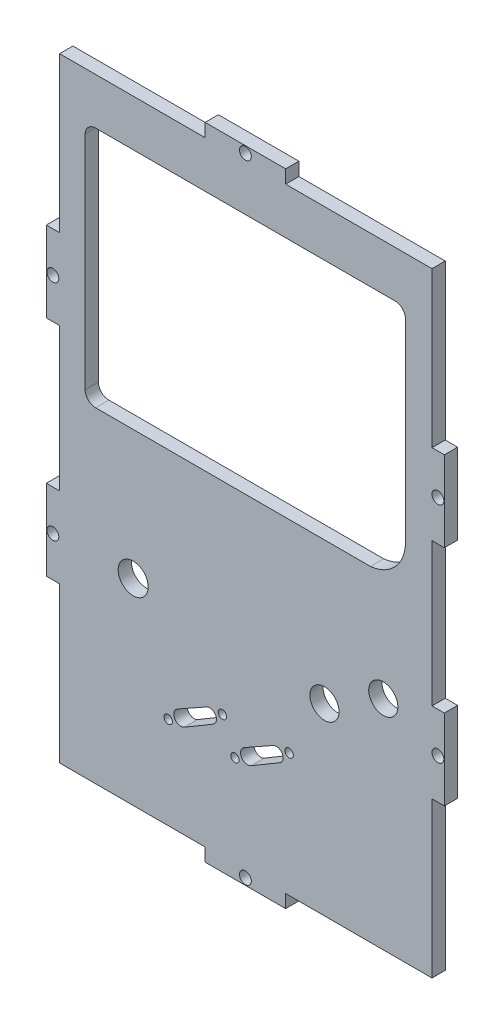
SolidWorks part; units mm, degrees
ref_plane "Front Plane" through (0, 0, 0) normal (0, 0, 1) x (1, 0, 0)
ref_plane "Top Plane" through (0, 0, 0) normal (0, 1, 0) x (1, 0, 0)
ref_plane "Right Plane" through (0, 0, 0) normal (1, 0, 0) x (0, 0, -1)
sketch "Sketch1" plane through (0, 0, 0) normal (0, 0, 1) x (1, 0, 0)
  line L0 (0.1058, 73.6301) -> (-0.0148, 62.4901) construction
  line L1 (-0.0148, 62.4901) -> (-0.0148, 56.2001) construction
  line L2 (-0.0148, 56.2001) -> (-0.0148, 10.268) construction
  line L3 (-15.4692, -49.8142) -> (-8.5409, -45.8142) construction
  line L4 (-15.4692, -49.8142) -> (0.5308, -49.8142)
  line L5 (0.5308, -49.8142) -> (7.4591, -45.8142) construction
  line L6 (-0.0148, 10.268) -> (0.1058, -73.6642) construction
  line L7 (-18.5002, -51.5642) -> (-5.5099, -44.0642) construction
  line L8 (0.5308, -49.8142) -> (7.4591, -45.8142)
  line L9 (-2.5002, -51.5642) -> (10.4901, -44.0642) construction
  line L15 (-16.3293, -29.1587) -> (-16.3293, -23.8757)
  line L20 (-0.2968, -48.3429) -> (6.6759, -44.4208)
  line L21 (8.2583, -47.1985) -> (1.3584, -51.2855)
  line L22 (-44.5392, 73.6301) -> (44.7508, 73.6301)
  line L23 (44.7508, 73.6301) -> (44.7508, -73.6642)
  line L24 (44.7508, -73.6642) -> (-44.5392, -73.6642)
  line L25 (-44.5392, -73.6642) -> (-44.5392, 73.6301)
  line L26 (-25.0598, 56.2001) -> (-25.0598, 10.268)
  line L27 (-25.0598, 10.268) -> (25.0303, 10.268)
  line L28 (25.0303, 10.268) -> (25.0303, 56.2001)
  line L29 (25.0303, 56.2001) -> (-25.0598, 56.2001)
  line L34 (35.8896, 62.4901) -> (-35.9192, 62.4901)
  line L35 (-38.4192, 59.9901) -> (-38.4192, 6.918)
  line L36 (-35.9192, 4.418) -> (29.9974, 4.418)
  line L37 (38.3896, 13.668) -> (38.3896, 59.9901)
  line L38 (-16.2968, -48.3429) -> (-9.3241, -44.4208)
  line L39 (-7.7417, -47.1985) -> (-14.6416, -51.2855)
  line L150 (42.2525, -55.0539) -> (42.2511, -54.9499)
  circle A1 centre (-5.5099, -44.0642) radius 1
  circle A2 centre (-26.9008, -26.5172) radius 3.6
  arc A3 (8.2583, -47.1985) -> (6.6759, -44.4208) centre (7.4591, -45.8142) ccw
  circle A4 centre (-18.5002, -51.5642) radius 1
  circle A5 centre (10.4901, -44.0642) radius 1
  arc A6 (-16.2968, -48.3429) -> (-14.6416, -51.2855) centre (-15.4692, -49.8142) ccw
  arc A7 (-7.7417, -47.1985) -> (-9.3241, -44.4208) centre (-8.5409, -45.8142) ccw
  circle A12 centre (-2.5002, -51.5642) radius 1
  circle A15 centre (18.9576, -29.5613) radius 3.5
  circle A16 centre (33.0683, -21.4917) radius 3.5
  arc A17 (-0.2968, -48.3429) -> (1.3584, -51.2855) centre (0.5308, -49.8142) ccw
  circle A19 centre (-32.8459, 40.326) radius 4.5
  arc A24 (38.3896, 59.9901) -> (35.8896, 62.4901) centre (35.8896, 59.9901) ccw
  arc A25 (-35.9192, 62.4901) -> (-38.4192, 59.9901) centre (-35.9192, 59.9901) ccw
  arc A26 (-38.4192, 6.918) -> (-35.9192, 4.418) centre (-35.9192, 6.918) ccw
  arc A27 (29.9974, 4.418) -> (38.3896, 13.668) centre (29.1397, 13.6282) ccw
  point P31 (-12.005, -47.8142)
  point P51 (3.995, -47.8142)
  dimension "D4" = 11.14
  dimension "D8" = 7
  dimension "D11" = 9
  dimension "D12" = 7.2
  dimension "D14" = 9.25
  dimension "D15" = 2.5
  dimension "D25" = 2
  dimension "D2" = 89.29
  dimension "D3" = 147.2943
  dimension "D5" = 25.9097
  dimension "D6" = 8.0696
  dimension "D7" = 14.1107
  dimension "D9" = 7.7861
  dimension "D10" = 22.1641
  dimension "D13" = 10.5715
  dimension "D16" = 6.29
  dimension "D17" = 6.12
  dimension "D18" = 5.85
  dimension "D19" = 16
  dimension "D20" = 8
  dimension "D21" = 29.07
  dimension "D22" = 23.85
  dimension "D23" = 30
  dimension "D24" = 15
extrude "Body" add sketch "Sketch1<7>" along normal blind 3.18 contours L25 L24 L23 L22 A27 L36 A26 L35 A25 L34 A24 L37 A17 L20 A3 L21 A16 A15 A7 L39 A6 L38 A2 region at (0.175, -16.7002, 0)
sketch "Sketch1<7>" plane through (0, 0, 0) normal (0, 0, 1) x (1, 0, 0) same geometry as "Sketch1"
extrude "Buttons" [suppressed] add sketch "Sketch1" along normal blind 3.18 contours A19 | A2 | L39 A7 L38 A6 | L20 A17 L21 A3 | A15 | A16
sketch "Sketch2" plane through (0, 73.6301, 0) normal (0, 1, 0) x (1, 0, 0)
  line L0 (-9.65, 0) -> (9.65, 0)
  line L1 (-44.5392, 0) -> (44.7508, 0) construction
  line L2 (9.65, 0) -> (9.65, -3.18)
  line L3 (-44.5392, -3.18) -> (44.7508, -3.18) construction
  line L4 (9.65, -3.18) -> (-9.65, -3.18)
  line L5 (-9.65, -3.18) -> (-9.65, 0)
  line L6 (0, 0) -> (0, -3.18) construction
  dimension "D1" = 19.3
extrude "Boss-Extrude1" add sketch "Sketch2" along normal blind 3.18
sketch "Sketch3" plane through (0, 0, 3.18) normal (0, 0, 1) x (1, 0, 0)
  line L0 (-9.65, 75.2201) -> (9.65, 75.2201) construction
  line L1 (-9.65, 76.8101) -> (-9.65, 73.6301) construction
  line L2 (9.65, 76.8101) -> (9.65, 73.6301) construction
  line L3 (0, 76.8101) -> (0, 73.4734) construction
  line L4 (-9.65, 76.8101) -> (9.65, 76.8101) construction
  circle A0 centre (0, 75.2201) radius 1.425
extrude "Cut-Extrude1" cut sketch "Sketch3" against normal through all
sketch "Sketch4" plane through (-44.5392, 0, 0) normal (-1, 0, 0) x (0, 0, 1)
  line L0 (0, 17.1601) -> (0, 36.4601)
  line L1 (0, -73.6642) -> (0, 73.6301) construction
  line L2 (0, 36.4601) -> (3.18, 36.4601)
  line L3 (3.18, -73.6642) -> (3.18, 73.6301) construction
  line L4 (3.18, 36.4601) -> (3.18, 17.1601)
  line L5 (3.18, 17.1601) -> (0, 17.1601)
  line L6 (3.18, 26.8101) -> (0, 26.8101) construction
  line L7 (0, 73.6301) -> (3.18, 73.6301) construction
  dimension "D1" = 19.3
  dimension "D2" = 46.82
extrude "Boss-Extrude2" add sketch "Sketch4" along normal blind 3.18
sketch "Sketch5" plane through (0, 0, 3.18) normal (0, 0, 1) x (1, 0, 0)
  line L0 (-47.7192, 26.8101) -> (-44.6033, 26.8101) construction
  line L1 (-47.7192, 17.1601) -> (-47.7192, 36.4601) construction
  line L2 (-46.1292, 17.1601) -> (-46.1292, 36.4601) construction
  line L3 (-47.7192, 17.1601) -> (-44.5392, 17.1601) construction
  line L4 (-47.7192, 36.4601) -> (-44.5392, 36.4601) construction
  circle A0 centre (-46.1612, 26.8101) radius 1.425
extrude "Cut-Extrude2" cut sketch "Sketch5" against normal through all
mirror "Mirror1" about plane through (0, 0, 0) normal (1, 0, 0) of "Cut-Extrude2", "Boss-Extrude2"
mirror "Mirror2" about plane through (0, 0, 0) normal (0, 1, 0) of "Cut-Extrude1", "Boss-Extrude1", "Mirror1"
